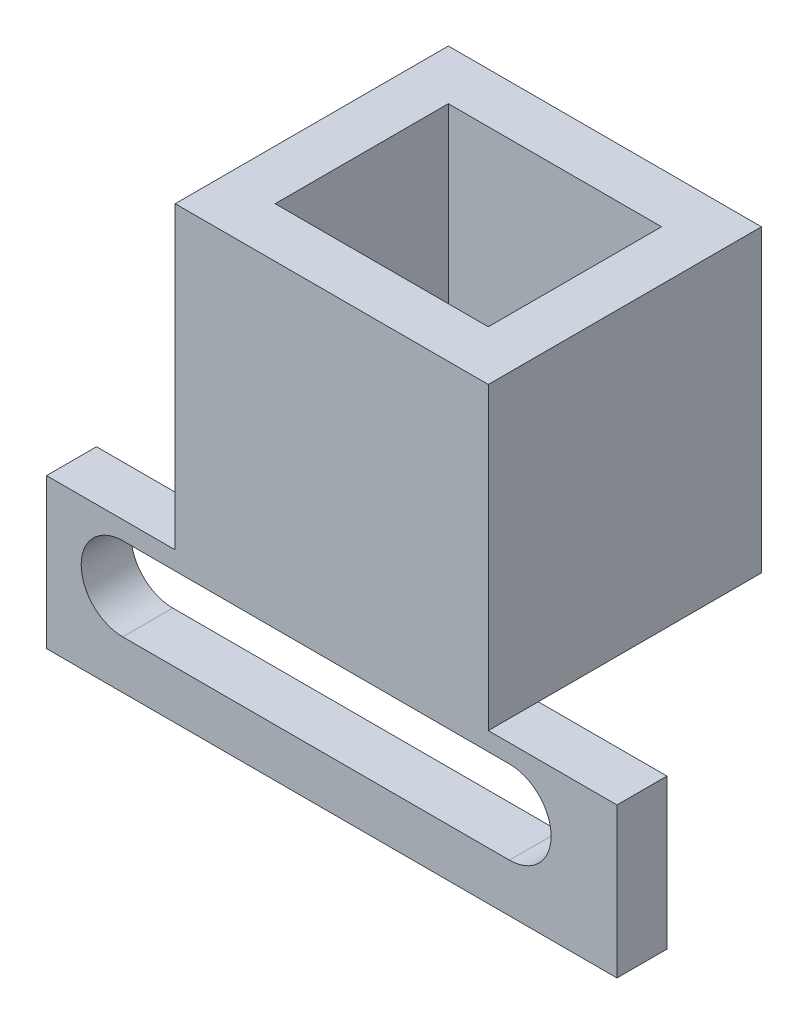
SolidWorks part; units mm, degrees
ref_plane "Front Plane" through (0, 0, 0) normal (0, 0, 1) x (1, 0, 0)
ref_plane "Top Plane" through (0, 0, 0) normal (0, 1, 0) x (1, 0, 0)
ref_plane "Right Plane" through (0, 0, 0) normal (1, 0, 0) x (0, 0, -1)
sketch "Sketch4" plane through (0, 0, -70.6082) normal (0, 0, -1) x (-1, 0, 0)
  line L0 (-46.2169, 93.8) -> (-46.2169, 82.2) construction
  line L1 (-69.0669, 81.5) -> (-45.8169, 81.5)
  line L2 (-69.0669, 81.5) -> (-69.0669, 96.6)
  line L4 (-45.8169, 81.5) -> (-45.8169, 96.6)
  line L5 (-68.6669, 82.2) -> (-68.6669, 93.8) construction
  line L6 (-46.5169, 81.9) -> (-68.3669, 81.9) construction
  line L7 (-45.8169, 96.6) -> (-40.3169, 96.6)
  line L8 (-40.3169, 96.6) -> (-40.3169, 78.6)
  line L9 (-40.3169, 78.6) -> (-74.5669, 78.6)
  line L10 (-74.5669, 78.6) -> (-74.5669, 96.6)
  line L11 (-74.5669, 96.6) -> (-69.0669, 96.6)
  line L12 (-68.3669, 94.1) -> (-46.5169, 94.1) construction
  dimension "D1" = 0.4
  dimension "D2" = 0.4
  dimension "D3" = 0.4
  dimension "D4" = 5.5
  dimension "D5" = 5.5
  dimension "D6" = 18
  dimension "D7" = 2.5
  dimension "D8" = 2.5
extrude "Boss-Extrude1" add sketch "Sketch4" along normal offset from surface (17.85 mm away) 0.4
sketch "Sketch5" plane through (0, 0, -88.4582) normal (0, 0, -1) x (-1, 0, 0)
  circle A0 centre (-43.7419, 88) radius 1
  arc A1 (-43.0041, 88.675) -> (-43.0041, 87.325) centre (-43.7419, 88) ccw construction
  circle A2 centre (-71.1419, 88) radius 1
  arc A3 (-71.8797, 87.325) -> (-71.8797, 88.675) centre (-71.1419, 88) ccw construction
extrude "Cut-Extrude1" cut sketch "Sketch5" against normal blind 10
sketch "Sketch6" plane through (0, 0, -70.6082) normal (0, 0, -1) x (-1, 0, 0)
  line L0 (-68.1119, 75) -> (-44.8968, 75) construction
  line L1 (-74.5669, 78.6) -> (-40.3169, 78.6)
  line L2 (-74.5669, 78.6) -> (-74.5669, 69.6)
  line L3 (-74.5669, 69.6) -> (-40.3169, 69.6)
  line L4 (-40.3169, 78.6) -> (-40.3169, 69.6)
  line L5 (-68.1119, 77.5) -> (-44.8968, 77.5)
  line L6 (-68.1119, 72.5) -> (-44.8968, 72.5)
  arc A4 (-68.1119, 77.5) -> (-68.1119, 72.5) centre (-68.1119, 75) ccw
  arc A5 (-44.8968, 72.5) -> (-44.8968, 77.5) centre (-44.8968, 75) ccw
  point P15 (-56.5044, 75)
  dimension "D2" = 2.5
  dimension "D1" = 9
  dimension "D3" = 3.6
  dimension "D4" = 6.455
extrude "Boss-Extrude2" add sketch "Sketch6" along normal blind 3
sketch "Sketch7" plane through (45.8169, 0, 0) normal (1, 0, 0) x (0, 0, -1)
  line L1 (70.6082, 96.6) -> (88.4582, 96.6)
  line L2 (70.6082, 96.6) -> (70.6082, 81.5)
  line L3 (70.6082, 81.5) -> (88.4582, 81.5)
  line L4 (88.4582, 96.6) -> (88.4582, 81.5)
extrude "Boss-Extrude3" add sketch "Sketch7" along normal blind 5.225
extrude "Boss-Extrude4" add sketch "Sketch7<3>" against normal blind 5.225 from surface starting at face at (69.0669, 89.05, -79.5332)
sketch "Sketch7<3>" plane through (45.8169, 0, 0) normal (1, 0, 0) x (0, 0, -1) same geometry as "Sketch7"
sketch "Sketch8" plane through (0, 0, -88.4582) normal (0, 0, -1) x (-1, 0, 0)
  line L0 (-40.3169, 78.6) -> (-74.5669, 78.6) construction
  line L1 (-74.5669, 96.6) -> (-66.8419, 96.6)
  line L2 (-74.5669, 96.6) -> (-74.5669, 78.6)
  line L3 (-74.5669, 78.6) -> (-66.8419, 78.6)
  line L4 (-66.8419, 96.6) -> (-66.8419, 78.6)
  line L5 (-40.3169, 96.6) -> (-51.0419, 96.6) construction
  line L6 (-40.3169, 78.6) -> (-48.0419, 78.6)
  line L7 (-40.3169, 78.6) -> (-40.3169, 96.6)
  line L8 (-40.3169, 96.6) -> (-48.0419, 96.6)
  line L9 (-48.0419, 78.6) -> (-48.0419, 96.6)
  line L10 (-51.0419, 81.5) -> (-51.0419, 96.6) construction
  line L11 (-63.8419, 96.6) -> (-63.8419, 81.5) construction
  dimension "D1" = 3
  dimension "D2" = 3
extrude "Cut-Extrude2" cut sketch "Sketch8" against normal up to next
sketch "Sketch9" plane through (0, 78.6, 0) normal (0, 1, 0) x (1, 0, 0)
  line L1 (40.3169, 73.6082) -> (74.5669, 73.6082)
  line L2 (40.3169, 73.6082) -> (40.3169, 70.6082)
  line L3 (40.3169, 70.6082) -> (74.5669, 70.6082)
  line L4 (74.5669, 73.6082) -> (74.5669, 70.6082)
extrude "Boss-Extrude5" add sketch "Sketch9" along normal up to surface (18 mm away) up to face at (49.5419, 96.6, -79.5332)
sketch "Sketch10" plane through (0, 0, -88.4582) normal (0, 0, -1) x (-1, 0, 0)
  line L0 (-66.8419, 78.6) -> (-48.0419, 78.6) construction
  line L1 (-63.8419, 81.5) -> (-51.0419, 81.5)
  line L2 (-63.8419, 81.5) -> (-63.8419, 78.6)
  line L3 (-63.8419, 78.6) -> (-51.0419, 78.6)
  line L4 (-51.0419, 81.5) -> (-51.0419, 78.6)
  point P7 (-51.0419, 81.5)
extrude "Cut-Extrude3" cut sketch "Sketch10" against normal up to surface (14.85 mm away) up to face at (57.4419, 85.35, -73.6082)
sketch "Sketch11" plane through (0, 0, -73.6082) normal (0, 0, -1) x (-1, 0, 0)
  line L1 (-74.5669, 96.6) -> (-66.8419, 96.6)
  line L2 (-74.5669, 96.6) -> (-74.5669, 78.6)
  line L3 (-74.5669, 78.6) -> (-66.8419, 78.6)
  line L4 (-66.8419, 96.6) -> (-66.8419, 78.6)
  line L5 (-48.0419, 78.6) -> (-40.3169, 78.6)
  line L6 (-48.0419, 78.6) -> (-48.0419, 96.6)
  line L7 (-48.0419, 96.6) -> (-40.3169, 96.6)
  line L8 (-40.3169, 78.6) -> (-40.3169, 96.6)
extrude "Cut-Extrude4" cut sketch "Sketch11" against normal up to next
sketch "Sketch12" plane through (0, 0, -88.4582) normal (0, 0, -1) x (-1, 0, 0)
  line L1 (-66.8419, 96.6) -> (-48.0419, 96.6)
  line L2 (-66.8419, 96.6) -> (-66.8419, 78.6)
  line L3 (-66.8419, 78.6) -> (-48.0419, 78.6)
  line L4 (-48.0419, 96.6) -> (-48.0419, 78.6)
extrude "Cut-Extrude5" cut sketch "Sketch12" against normal blind 4.45
sketch "Sketch13" plane through (0, 0, -84.0082) normal (0, 0, -1) x (-1, 0, 0)
  line L1 (-66.8419, 96.6) -> (-48.0419, 96.6)
  line L2 (-66.8419, 96.6) -> (-66.8419, 78.6)
  line L3 (-66.8419, 78.6) -> (-48.0419, 78.6)
  line L4 (-48.0419, 96.6) -> (-48.0419, 78.6)
extrude "Boss-Extrude6" add sketch "Sketch13" along normal blind 3
